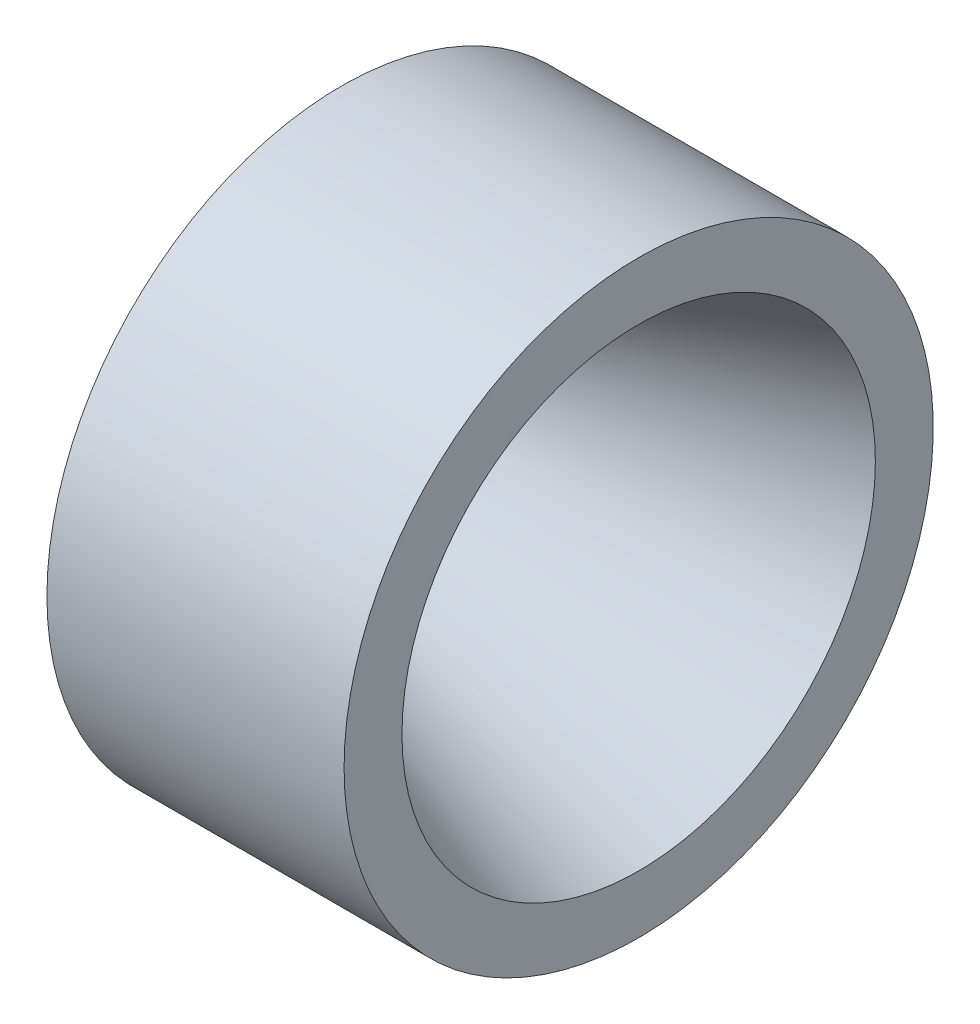
SolidWorks part; units mm, degrees
material "1023 Carbon Steel Sheet (SS)"
ref_plane "Front Plane" through (0, 0, 0) normal (0, 0, 1) x (1, 0, 0)
ref_plane "Top Plane" through (0, 0, 0) normal (0, 1, 0) x (1, 0, 0)
ref_plane "Right Plane" through (0, 0, 0) normal (1, 0, 0) x (0, 0, -1)
sketch "Sketch1" plane through (0, 0, 0) normal (0, 0, 1) x (1, 0, 0)
  line L0 (0, 0) -> (280.924, 0) construction
  line L1 (280.924, 0) -> (280.911, 30.48) construction
  line L3 (280.911, 30.48) -> (351.3696, 56.1248)
  line L4 (280.924, 0) -> (534.924, 0) construction
  line L5 (351.3696, 56.1248) -> (351.3696, 69.85)
  line L6 (280.911, 30.48) -> (280.911, 50.8)
  line L8 (280.911, 50.8) -> (280.911, 69.85)
  line L9 (280.911, 69.85) -> (351.3696, 69.85)
  dimension "D1" = 280.924
  dimension "D2" = 30.48
  dimension "D3" = 254
  dimension "D4" = 20
  dimension "D5" = 56.1248
  dimension "D6" = 139.7
  dimension "D7" = 20.32
revolve "Revolve1" add sketch "Sketch1" angle 360 about L0
sketch "Sketch2" plane through (0, 0, 0) normal (0, 0, 1) x (1, 0, 0)
  line L0 (280.911, 30.48) -> (280.911, -30.48) construction
  point P0 (280.911, 0)
sketch "Sketch4" plane through (280.911, 0, 0) normal (-1, 0, 0) x (0, 0, 1)
  line L0 (0, 0) -> (0, 59.69)
  circle A0 centre (0, 59.69) radius 2.54
  dimension "D2" = 5.08
  dimension "D1" = 59.69
extrude "Cut-Extrude1" cut sketch "Sketch4" against normal blind 30.48 contours A0 region at (280.911, 57.9447, 1.7453)
pattern_circular "CirPattern1" count 12 over 360 about axis through (280.911, 0, 0) along (-1, 0, 0) of "Cut-Extrude1"
